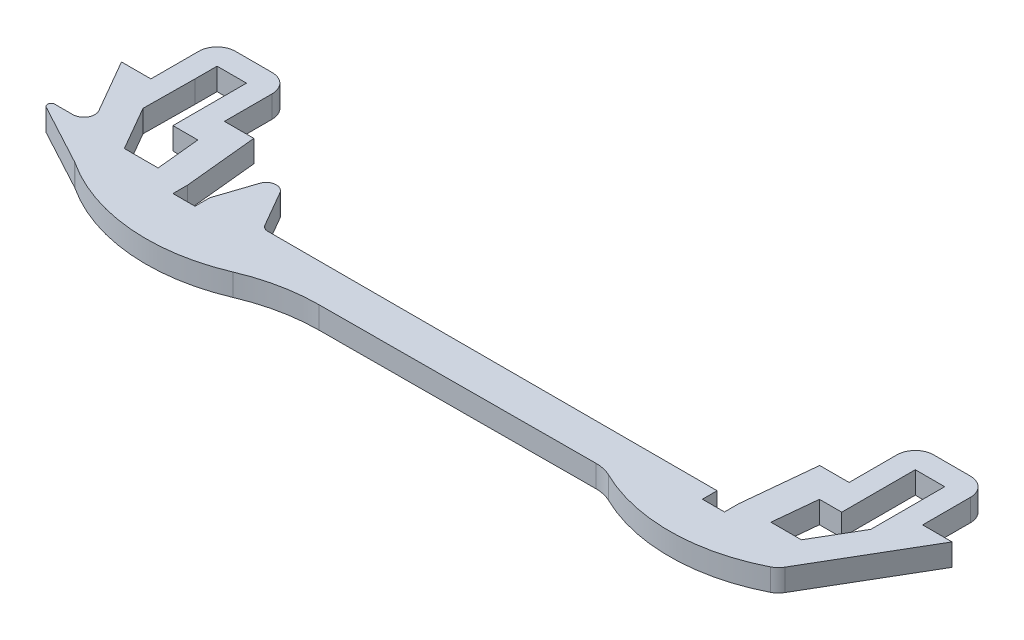
SolidWorks part; units mm, degrees
material "Custom Plastic"
ref_plane "Front Plane" through (0, 0, 0) normal (0, 0, 1) x (1, 0, 0)
ref_plane "Top Plane" through (0, 0, 0) normal (0, 1, 0) x (1, 0, 0)
ref_plane "Right Plane" through (0, 0, 0) normal (1, 0, 0) x (0, 0, -1)
sketch "Sketch1" plane through (0, 0, 0) normal (0, 1, 0) x (1, 0, 0)
  line L0 (-62.4186, -47.1375) -> (-58.4186, -47.1375)
  line L1 (-58.4186, -47.1375) -> (-58.4186, -38.1375)
  line L2 (-58.4186, -38.1375) -> (-48.4186, -38.1375)
  line L3 (-48.4186, -38.1375) -> (-48.4186, -47.1375)
  line L4 (-48.4186, -47.1375) -> (-44.4186, -47.1375)
  line L5 (-44.4186, -47.1375) -> (-43.4188, -57.135)
  line L7 (31.5814, -57.1876) -> (32.5814, -47.1902)
  line L8 (32.5814, -47.1902) -> (36.5814, -47.1902)
  line L9 (36.5814, -47.1902) -> (36.5814, -38.1902)
  line L10 (36.5814, -38.1902) -> (46.5814, -38.1902)
  line L11 (46.5814, -38.1902) -> (46.5814, -47.1902)
  line L12 (46.5814, -47.1902) -> (50.5814, -47.1902)
  line L13 (50.5814, -47.1902) -> (41.8306, -62.1375)
  line L15 (-58.2259, -54.3993) -> (-62.4186, -47.1375)
  line L16 (36.5478, -51.1902) -> (39.5814, -51.1902)
  line L17 (-55.4186, -41.1375) -> (-51.4186, -41.1375)
  line L18 (-55.4186, -41.1375) -> (-55.4186, -44.1379)
  line L20 (-51.4186, -41.1375) -> (-51.4186, -44.1375)
  line L21 (39.5814, -41.1902) -> (43.5814, -41.1902)
  line L22 (39.5814, -41.1902) -> (39.5814, -44.1902)
  line L24 (43.5814, -41.1902) -> (43.5814, -44.2297)
  line L25 (43.5814, -51.2297) -> (40.0934, -57.1876)
  line L26 (40.0934, -57.1876) -> (35.9479, -57.1876)
  line L27 (35.9479, -57.1876) -> (36.5478, -51.1902)
  line L28 (-51.4186, -51.1375) -> (-48.0385, -51.1375)
  line L29 (-48.0385, -51.1375) -> (-47.4385, -57.1375)
  line L30 (-47.4385, -57.1375) -> (-52.0263, -57.1375)
  line L31 (-52.0263, -57.1375) -> (-55.4904, -51.1375)
  line L32 (28.5814, -57.1375) -> (28.5814, -59.1375)
  line L33 (28.5814, -47.1375) -> (28.5814, -62.1375) construction
  line L34 (28.5814, -59.1375) -> (31.5814, -59.1375)
  line L35 (31.5814, -59.1375) -> (31.5814, -57.1876)
  line L36 (31.5814, -62.1375) -> (31.5814, -47.1375) construction
  line L38 (-43.4188, -57.135) -> (-43.4188, -59.1375)
  line L39 (-43.4188, -59.1375) -> (-40.4188, -59.1375)
  line L40 (-40.4188, -59.1375) -> (-40.4188, -57.1375)
  line L41 (-33.1369, -57.1375) -> (28.5814, -57.1375)
  line L42 (-33.1369, -57.1375) -> (-36.236, -51.7698)
  line L43 (43.5814, -44.2297) -> (43.5814, -51.2297)
  line L44 (-38.7227, -52.0235) -> (-40.4188, -57.1375)
  line L45 (39.5814, -44.1902) -> (39.5814, -51.1902)
  line L46 (-55.4186, -44.1379) -> (-55.4904, -51.1375)
  line L47 (-51.4186, -44.1375) -> (-51.4186, -51.1375)
  line L48 (-53.7583, -62.1375) -> (-62.2024, -57.5896)
  line L49 (-61.9653, -56.6493) -> (-59.525, -56.6493)
  line L50 (30.0814, -59.1375) -> (30.0814, -65.1375) construction
  line L51 (18.3323, -62.1375) -> (-26.3644, -62.3233)
  arc A0 (-38.7227, -52.0235) -> (-36.236, -51.7698) centre (-37.4224, -52.4548) cw
  arc A1 (-59.525, -56.6493) -> (-58.2259, -54.3993) centre (-59.525, -55.1493) ccw
  arc A2 (-62.2024, -57.5896) -> (-61.9653, -56.6493) centre (-61.9653, -57.1493) cw
  arc A3 (41.8306, -62.1375) -> (18.3323, -62.1375) centre (30.0814, -40.6304) cw
  arc A4 (-53.7583, -62.1375) -> (-26.3644, -62.3233) centre (-39.9188, -41.2179) ccw
  point P58 (30.0814, -59.1375)
  point P61 (-41.9188, -40.2752)
  point P62 (-41.9188, -59.1375)
  point P63 (0, 0)
  point P64 (0, 0)
  point P65 (-26.8882, -62.1375)
  dimension "D6" = 0.5
  dimension "D5" = 1.5
  dimension "D2" = 4
  dimension "D3" = 9
  dimension "D4" = 3
  dimension "D7" = 2
  dimension "D8" = 10
  dimension "D9" = 85
  dimension "D10" = 3
  dimension "D11" = 95.5889
  dimension "D12" = 3
  dimension "D13" = 3
  dimension "D14" = 3
  dimension "D15" = 3
  dimension "D16" = 14.9473
  dimension "D17" = 4
  dimension "D18" = 4
  dimension "D19" = 4
  dimension "D20" = 4
  dimension "D21" = 4
  dimension "D22" = 7.2618
  dimension "D23" = 2
  dimension "D24" = 3
  dimension "D25" = 2.4403
  dimension "D26" = 4.548
  dimension "D27" = 9.9975
  dimension "D28" = 0.9997
  dimension "D29" = 1
  dimension "D30" = 11.9473
  dimension "D31" = 4.6827
  dimension "D32" = 120
  dimension "D33" = 2.9964
  dimension "D34" = 5.114
  dimension "D35" = 4
  dimension "D36" = 4.5877
  dimension "D37" = 7
  dimension "D38" = 7
  dimension "D39" = 2
  dimension "D40" = 6
extrude "Boss-Extrude1" add sketch "Sketch1" along normal blind 3
fillet "Fillet2" radius 2.5 4 edges at (46.5814, 1.5, 38.1902) (36.5814, 1.5, 38.1902) (-58.4186, 1.5, 38.1375) (-48.4186, 1.5, 38.1375)
fillet "Fillet3" radius 1 1 edges at (-33.1369, 1.5, 57.1375)
fillet "Fillet5" radius 2.5 2 edges at (-53.7583, 1.5, 62.1375) (41.8306, 1.5, 62.1375)
fillet "Fillet6" radius 5 1 edges at (18.3323, 1.5, 62.1375)
fillet "Fillet7" radius 25 1 edges at (-26.3644, 1.5, 62.3233)
